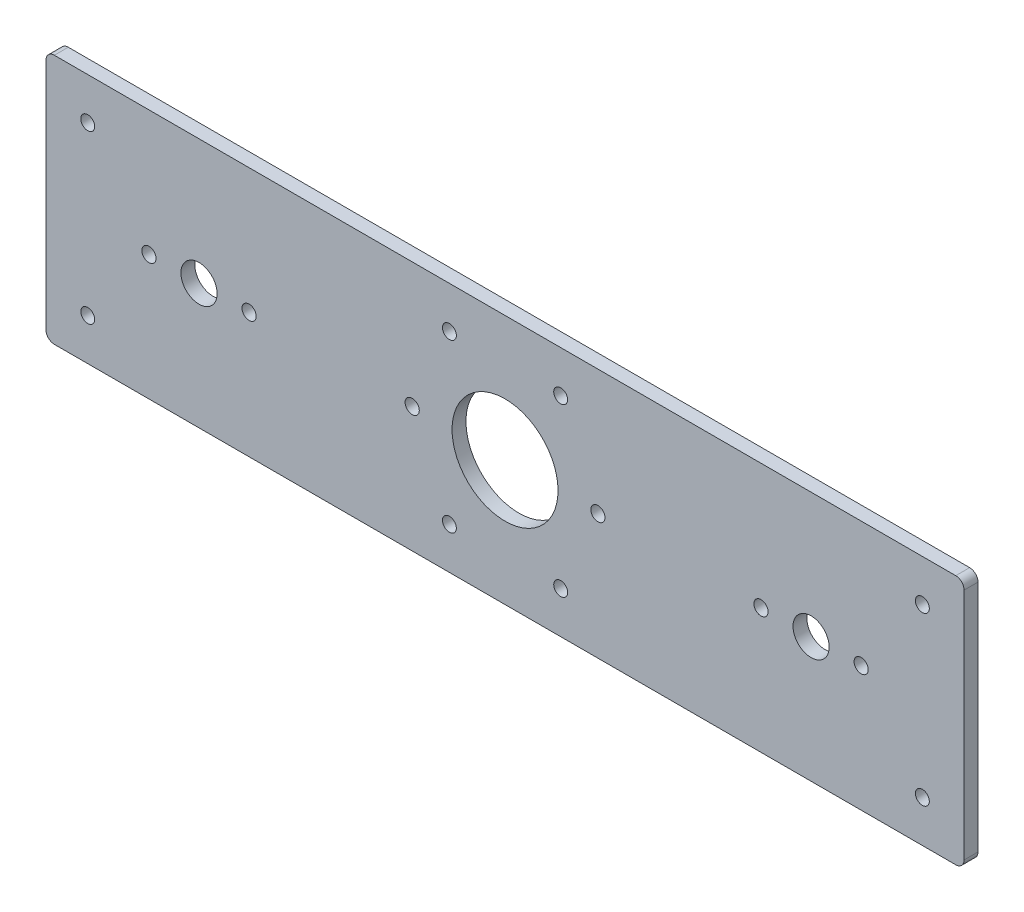
SolidWorks part; units mm, degrees
ref_plane "Front Plane" through (0, 0, 0) normal (0, 0, 1) x (1, 0, 0)
ref_plane "Top Plane" through (0, 0, 0) normal (0, 1, 0) x (1, 0, 0)
ref_plane "Right Plane" through (0, 0, 0) normal (1, 0, 0) x (0, 0, -1)
sketch "Sketch1" plane through (0, 0, 0) normal (0, 0, 1) x (1, 0, 0)
  line L0 (-165, 0) -> (165, 0) construction
  line L1 (165, -45) -> (-165, -45)
  line L2 (165, -45) -> (165, 45)
  line L3 (165, 45) -> (-165, 45)
  line L4 (-165, -45) -> (-165, 45)
  line L5 (165, -45) -> (-165, 45) construction
  line L6 (165, 45) -> (-165, -45) construction
  line L8 (0, -33.3754) -> (33.3754, 0) construction
  line L9 (0, -33.3754) -> (-33.3754, 0) construction
  line L10 (-33.3754, 0) -> (0, 33.3754) construction
  line L11 (33.3754, 0) -> (0, 33.3754) construction
  line L12 (0, -33.3754) -> (0, 33.3754) construction
  line L13 (-33.3754, 0) -> (33.3754, 0) construction
  circle A0 centre (0, 0) radius 19.05
  circle A1 centre (-33.3754, 0) radius 2.55
  circle A2 centre (33.3754, 0) radius 2.55
  point P0 (0, 0)
  dimension "D3" = 38.1
  dimension "D4" = 47.2
  dimension "D5" = 47.2
  dimension "D8" = 5.1
  dimension "D9" = 5.1
  dimension "D1" = 90
  dimension "D2" = 330
  dimension "D6" = 90
  dimension "D7" = 90
extrude "Boss-Extrude1" add sketch "Sketch1" along normal mid plane 5
sketch "Sketch2" plane through (0, 0, 2.5) normal (0, 0, 1) x (1, 0, 0)
  line L2 (-150, 45) -> (-150, -45)
  line L3 (-150, 45) -> (-150, -45) construction
  line L5 (150, -45) -> (150, 45)
  line L6 (150, -45) -> (150, 45) construction
  line L23 (165, 30) -> (-165, 30)
  line L24 (165, 30) -> (-165, 30) construction
  line L25 (0, 45) -> (0, -45) construction
  line L26 (-165, -30) -> (165, -30)
  line L27 (-165, -30) -> (165, -30) construction
  line L28 (165, 45) -> (-165, 45) construction
  line L29 (-165, -45) -> (165, -45) construction
  line L30 (-20, 45) -> (-20, -45) construction
  line L31 (20, 45) -> (20, -45) construction
  circle A0 centre (-150, 30) radius 2.5
  circle A1 centre (-150, -30) radius 2.5
  circle A2 centre (-20, 30) radius 2.5
  circle A3 centre (-20, -30) radius 2.5
  circle A4 centre (20, -30) radius 2.5
  circle A5 centre (20, 30) radius 2.5
  circle A6 centre (150, 30) radius 2.5
  circle A7 centre (150, -30) radius 2.5
  dimension "D7" = 5
  dimension "D8" = 5
  dimension "D9" = 5
  dimension "D10" = 5
  dimension "D11" = 5
  dimension "D12" = 5
  dimension "D13" = 5
  dimension "D14" = 5
  dimension "D1" = 15
  dimension "D2" = 15
  dimension "D3" = 15
  dimension "D4" = 15
  dimension "D5" = 20
  dimension "D6" = 20
extrude "Cut-Extrude1" cut sketch "Sketch2" against normal through all
sketch "Sketch3" plane through (0, 0, 2.5) normal (0, 0, 1) x (1, 0, 0)
  line L0 (0, 0) -> (-49.4534, 0) construction
  circle A0 centre (-92, 0) radius 2.55
  circle A1 centre (-128, 0) radius 2.55
  circle A2 centre (-110, 0) radius 6.5
  dimension "D1" = 5.1
  dimension "D2" = 5.1
  dimension "D3" = 13
  dimension "D4" = 110
  dimension "D5" = 18
  dimension "D6" = 18
extrude "Cut-Extrude2" cut sketch "Sketch3" against normal through all
mirror "Mirror1" about plane through (0, 0, 0) normal (1, 0, 0) of "Cut-Extrude2"
fillet "Fillet1" radius 3 4 edges at (-165, -45, 0) (165, -45, 0) (165, 45, 0) (-165, 45, 0)
